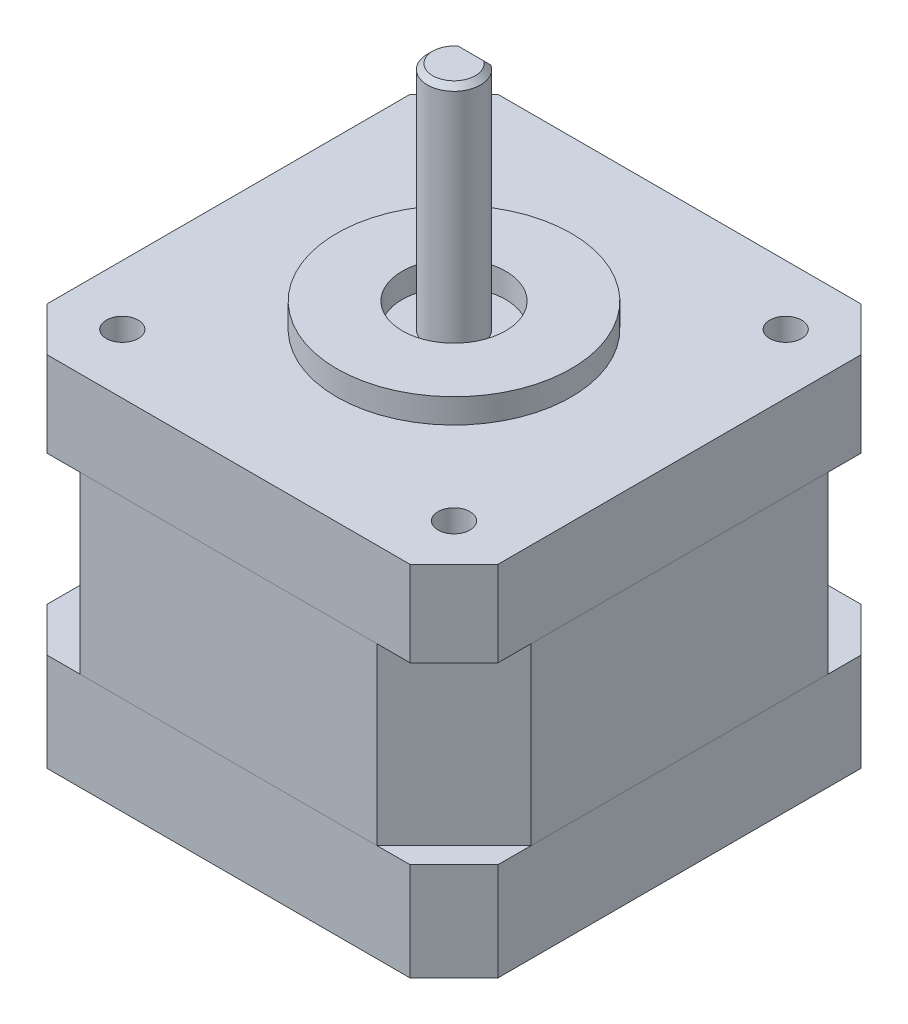
SolidWorks part; units mm, degrees
ref_plane "Front Plane" through (0, 0, 0) normal (0, 0, 1) x (1, 0, 0)
ref_plane "Top Plane" through (0, 0, 0) normal (0, 1, 0) x (1, 0, 0)
ref_plane "Right Plane" through (0, 0, 0) normal (1, 0, 0) x (0, 0, -1)
sketch "Sketch1" plane through (0, 0, 0) normal (0, 1, 0) x (1, 0, 0)
  line L0 (-21.15, 17.0338) -> (-17.0338, 21.15)
  line L1 (-21.15, 21.15) -> (21.15, 21.15)
  line L2 (-21.15, 21.15) -> (-21.15, -21.15)
  line L3 (-21.15, -21.15) -> (21.15, -21.15)
  line L4 (21.15, 21.15) -> (21.15, -21.15)
  line L5 (-21.15, 21.15) -> (21.15, -21.15) construction
  line L6 (-21.15, -21.15) -> (21.15, 21.15) construction
  line L7 (17.0338, -21.15) -> (21.15, -17.0338)
  line L8 (0, 0) -> (49.8859, 0) construction
  line L9 (-21.15, -17.0338) -> (-17.0338, -21.15)
  line L10 (17.0338, 21.15) -> (21.15, 17.0338)
  point P0 (0, 0)
  dimension "D1" = 42.3
  dimension "D2" = 54
  dimension "D3" = 45
extrude "BottomBase" add sketch "Sketch1" along normal blind 9.2 contours L10 L1 L0 L2 L9 L3 L7 L4 region at (0, 0, 0)
sketch "Sketch2" plane through (0, 9.2, 0) normal (0, 1, 0) x (1, 0, 0)
  line L0 (13.9225, -21.15) -> (21.15, -13.9225)
  line L1 (-17.0338, -21.15) -> (17.0338, -21.15) construction
  line L2 (21.15, 17.0338) -> (21.15, -17.0338) construction
  line L3 (0, 0) -> (3.1599, 0) construction
  line L4 (0, 0) -> (0, 4.2752) construction
  line L5 (17.0338, -21.15) -> (21.15, -17.0338) construction
  line L6 (13.9225, 21.15) -> (21.15, 13.9225)
  line L7 (-13.9225, -21.15) -> (-21.15, -13.9225)
  line L8 (-13.9225, 21.15) -> (-21.15, 13.9225)
  line L9 (-21.15, 13.9225) -> (-21.15, -13.9225)
  line L10 (-13.9225, 21.15) -> (13.9225, 21.15)
  line L11 (21.15, 13.9225) -> (21.15, -13.9225)
  line L12 (-13.9225, -21.15) -> (13.9225, -21.15)
  dimension "D1" = 2.2
extrude "MiddleBase" add sketch "Sketch2" along normal blind 16.4 separate body
sketch "Sketch3" plane through (0, 25.6, 0) normal (0, 1, 0) x (1, 0, 0)
  line L8 (21.15, 17.0338) -> (17.0338, 21.15)
  line L9 (21.15, -17.0338) -> (21.15, 17.0338)
  line L10 (17.0338, -21.15) -> (21.15, -17.0338)
  line L11 (-17.0338, -21.15) -> (17.0338, -21.15)
  line L12 (-21.15, -17.0338) -> (-17.0338, -21.15)
  line L13 (-21.15, 17.0338) -> (-21.15, -17.0338)
  line L14 (-17.0338, 21.15) -> (-21.15, 17.0338)
  line L15 (17.0338, 21.15) -> (-17.0338, 21.15)
  line L16 (21.15, 17.0338) -> (17.0338, 21.15)
  line L17 (21.15, -17.0338) -> (21.15, 17.0338)
  line L18 (17.0338, -21.15) -> (21.15, -17.0338)
  line L19 (-17.0338, -21.15) -> (17.0338, -21.15)
  line L20 (-21.15, -17.0338) -> (-17.0338, -21.15)
  line L21 (-21.15, 17.0338) -> (-21.15, -17.0338)
  line L22 (-17.0338, 21.15) -> (-21.15, 17.0338)
  line L23 (17.0338, 21.15) -> (-17.0338, 21.15)
  dimension "D1" = 0
extrude "TopBase" add sketch "Sketch3" along normal blind 8 separate body
sketch "Sketch4" plane through (0, 33.6, 0) normal (0, 1, 0) x (1, 0, 0)
  line L0 (21.15, 17.0338) -> (17.0338, 21.15) construction
  line L1 (0, 0) -> (19.0919, 19.0919) construction
  circle A0 centre (15.5563, 15.5563) radius 1.5
  circle A1 centre (15.5563, -15.5563) radius 1.5
  circle A2 centre (-15.5563, -15.5563) radius 1.5
  circle A3 centre (-15.5563, 15.5563) radius 1.5
  point P16 (0, 0)
  dimension "D1" = 3
  dimension "D2" = 5
  dimension "D3" = 4
extrude "MountingHoles" cut sketch "Sketch4" against normal blind 5
sketch "Sketch5" plane through (0, 33.6, 0) normal (0, 1, 0) x (1, 0, 0)
  circle A0 centre (0, 0) radius 11
  dimension "D1" = 22
extrude "RingAroundAxel" add sketch "Sketch5" along normal blind 2.3
sketch "Sketch6" plane through (0, 35.9, 0) normal (0, 1, 0) x (1, 0, 0)
  circle A0 centre (0, 0) radius 4.85
  dimension "D1" = 9.7
extrude "InnerCutoutAroundAxel" cut sketch "Sketch6" against normal blind 3.6
sketch "Sketch9" plane through (-21.15, 0, 0) normal (-1, 0, 0) x (0, 0, 1)
  line L1 (-3.65, 8.45) -> (3.65, 8.45)
  line L2 (-3.65, 8.45) -> (-3.65, 2)
  line L3 (-3.65, 2) -> (3.65, 2)
  line L4 (3.65, 8.45) -> (3.65, 2)
  line L6 (-17.0338, 0) -> (17.0338, 0) construction
  point P5 (0, 2)
  point P14 (0, 0)
  dimension "D1" = 7.3
  dimension "D2" = 6.45
  dimension "D3" = 2
extrude "Wires" cut sketch "Sketch9" against normal blind 2
sketch "Sketch10" plane through (0, 33.6, 0) normal (0, 1, 0) x (1, 0, 0)
  circle A0 centre (0, 0) radius 2.5
  dimension "D1" = 5
extrude "Axel" add sketch "Sketch10" along normal blind 21.6
sketch "Sketch11" plane through (0, 55.2, 0) normal (0, 1, 0) x (1, 0, 0)
  line L0 (-1.3565, 2.1) -> (1.3565, 2.1)
  line L1 (0, -2.5) -> (6.7536, -2.5) construction
  circle A0 centre (0, 0) radius 2.5 construction
  circle A1 centre (0, 0) radius 2.5 construction
  arc A2 (-1.3565, 2.1) -> (1.3565, 2.1) centre (0, 0) cw
  dimension "D1" = 4.6
extrude "FlatFaceOfAxel" cut sketch "Sketch11" against normal blind 15
chamfer "Chamfer1" distance 0.5 angle 45 2 edges at (0, 55.2, -2.1) (0, 55.2, 2.5)
